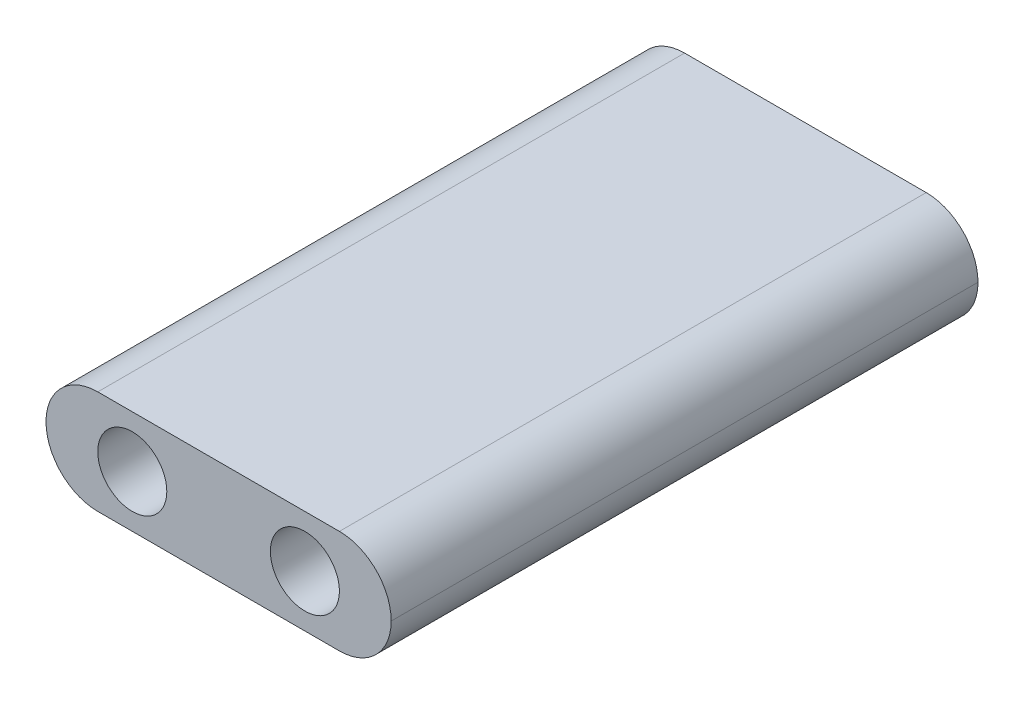
SolidWorks part; units mm, degrees
ref_plane "Front Plane" through (0, 0, 0) normal (0, 0, 1) x (1, 0, 0)
ref_plane "Top Plane" through (0, 0, 0) normal (0, 1, 0) x (1, 0, 0)
ref_plane "Right Plane" through (0, 0, 0) normal (1, 0, 0) x (0, 0, -1)
sketch "Sketch2" plane through (0, 0, 0) normal (0, 0, 1) x (1, 0, 0)
  line L1 (-10, -3) -> (10, -3)
  line L2 (-10, -3) -> (-10, 3)
  line L3 (-10, 3) -> (10, 3)
  line L4 (10, -3) -> (10, 3)
  line L5 (-10, -3) -> (10, 3) construction
  line L6 (-10, 3) -> (10, -3) construction
  point P0 (0, 0)
  dimension "D1" = 6
  dimension "D2" = 20
extrude "Boss-Extrude1" add sketch "Sketch2" along normal blind 34
sketch "Sketch3" plane through (0, 0, 34) normal (0, 0, 1) x (1, 0, 0)
  line L0 (0, 0) -> (-5, 0)
  line L1 (0, 0) -> (5, 0)
  circle A0 centre (-5, 0) radius 2
  circle A1 centre (5, 0) radius 2
  dimension "D2" = 4
  dimension "D4" = 4
  dimension "D1" = 5
  dimension "D3" = 5
extrude "Cut-Extrude1" cut sketch "Sketch3" against normal blind 34 contours A0 | A1 region at (-6.9434, 0, 34) region at (5, 1.9434, 34)
fillet "Fillet1" radius 3 4 edges at (10, -3, 17) (10, 3, 17) (-10, -3, 17) (-10, 3, 17)
